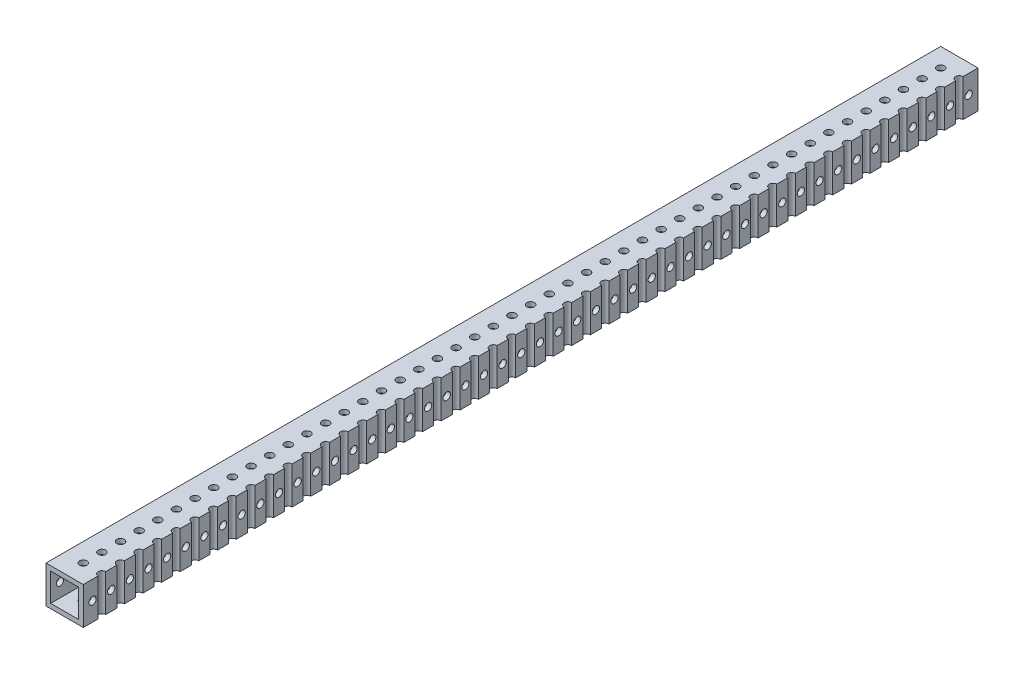
SolidWorks part; units mm, degrees
material "6061-T6 (SS)"
ref_plane "Front Plane" through (0, 0, 0) normal (0, 0, 1) x (1, 0, 0)
ref_plane "Top Plane" through (0, 0, 0) normal (0, 1, 0) x (1, 0, 0)
ref_plane "Right Plane" through (0, 0, 0) normal (1, 0, 0) x (0, 0, -1)
sketch "Sketch1" plane through (0, 0, 0) normal (0, 0, 1) x (1, 0, 0)
  line L0 (-9.525, 9.525) -> (9.525, 9.525)
  line L1 (-12.7, 12.7) -> (12.7, 12.7)
  line L2 (-12.7, 12.7) -> (-12.7, -12.7)
  line L3 (-12.7, -12.7) -> (12.7, -12.7)
  line L4 (12.7, 12.7) -> (12.7, -12.7)
  line L5 (9.525, 9.525) -> (9.525, -9.525)
  line L6 (-9.525, -9.525) -> (9.525, -9.525)
  line L7 (-9.525, 9.525) -> (-9.525, -9.525)
  line L8 (-12.7, 12.7) -> (12.7, -12.7) construction
  line L9 (12.7, 12.7) -> (-12.7, -12.7) construction
  point P5 (0, 0)
  dimension "D1" = 25.4
  dimension "D2" = 25.4
  dimension "D3" = 3.175
extrude "Boss-Extrude1" add sketch "Sketch1" along normal mid plane 609.6
sketch "Sketch2" plane through (0, 12.7, 0) normal (0, 1, 0) x (1, 0, 0)
  line L0 (12.7, -304.8) -> (-12.7, -304.8) construction
  line L1 (-12.7, -304.8) -> (-12.7, 304.8) construction
  line L2 (0, -292.1) -> (12.7, -292.1) construction
  line L3 (12.7, -292.1) -> (25.4, -292.1) construction
  line L4 (12.7, 304.8) -> (-12.7, 304.8) construction
  circle A0 centre (12.7, -292.1) radius 2.5527
  circle A1 centre (25.4, -292.1) radius 2.5527
  circle A2 centre (0, -292.1) radius 2.5527
  circle A3 centre (0, -279.4) radius 2.5527
  circle A4 centre (12.7, -279.4) radius 2.5527
  circle A5 centre (25.4, -279.4) radius 2.5527
  circle A6 centre (0, -266.7) radius 2.5527
  circle A7 centre (12.7, -266.7) radius 2.5527
  circle A8 centre (25.4, -266.7) radius 2.5527
  circle A9 centre (0, -254) radius 2.5527
  circle A10 centre (12.7, -254) radius 2.5527
  circle A11 centre (25.4, -254) radius 2.5527
  circle A12 centre (0, -241.3) radius 2.5527
  circle A13 centre (12.7, -241.3) radius 2.5527
  circle A14 centre (25.4, -241.3) radius 2.5527
  circle A15 centre (0, -228.6) radius 2.5527
  circle A16 centre (12.7, -228.6) radius 2.5527
  circle A17 centre (25.4, -228.6) radius 2.5527
  circle A18 centre (0, -215.9) radius 2.5527
  circle A19 centre (12.7, -215.9) radius 2.5527
  circle A20 centre (25.4, -215.9) radius 2.5527
  circle A21 centre (0, -203.2) radius 2.5527
  circle A22 centre (12.7, -203.2) radius 2.5527
  circle A23 centre (25.4, -203.2) radius 2.5527
  circle A24 centre (0, -190.5) radius 2.5527
  circle A25 centre (12.7, -190.5) radius 2.5527
  circle A26 centre (25.4, -190.5) radius 2.5527
  circle A27 centre (0, -177.8) radius 2.5527
  circle A28 centre (12.7, -177.8) radius 2.5527
  circle A29 centre (25.4, -177.8) radius 2.5527
  circle A30 centre (0, -165.1) radius 2.5527
  circle A31 centre (12.7, -165.1) radius 2.5527
  circle A32 centre (25.4, -165.1) radius 2.5527
  circle A33 centre (0, -152.4) radius 2.5527
  circle A34 centre (12.7, -152.4) radius 2.5527
  circle A35 centre (25.4, -152.4) radius 2.5527
  circle A36 centre (0, -139.7) radius 2.5527
  circle A37 centre (12.7, -139.7) radius 2.5527
  circle A38 centre (25.4, -139.7) radius 2.5527
  circle A39 centre (0, -127) radius 2.5527
  circle A40 centre (12.7, -127) radius 2.5527
  circle A41 centre (25.4, -127) radius 2.5527
  circle A42 centre (0, -114.3) radius 2.5527
  circle A43 centre (12.7, -114.3) radius 2.5527
  circle A44 centre (25.4, -114.3) radius 2.5527
  circle A45 centre (0, -101.6) radius 2.5527
  circle A46 centre (12.7, -101.6) radius 2.5527
  circle A47 centre (25.4, -101.6) radius 2.5527
  circle A48 centre (0, -88.9) radius 2.5527
  circle A49 centre (12.7, -88.9) radius 2.5527
  circle A50 centre (25.4, -88.9) radius 2.5527
  circle A51 centre (0, -76.2) radius 2.5527
  circle A52 centre (12.7, -76.2) radius 2.5527
  circle A53 centre (25.4, -76.2) radius 2.5527
  circle A54 centre (0, -63.5) radius 2.5527
  circle A55 centre (12.7, -63.5) radius 2.5527
  circle A56 centre (25.4, -63.5) radius 2.5527
  circle A57 centre (0, -50.8) radius 2.5527
  circle A58 centre (12.7, -50.8) radius 2.5527
  circle A59 centre (25.4, -50.8) radius 2.5527
  circle A60 centre (0, -38.1) radius 2.5527
  circle A61 centre (12.7, -38.1) radius 2.5527
  circle A62 centre (25.4, -38.1) radius 2.5527
  circle A63 centre (0, -25.4) radius 2.5527
  circle A64 centre (12.7, -25.4) radius 2.5527
  circle A65 centre (25.4, -25.4) radius 2.5527
  circle A66 centre (0, -12.7) radius 2.5527
  circle A67 centre (12.7, -12.7) radius 2.5527
  circle A68 centre (25.4, -12.7) radius 2.5527
  circle A69 centre (0, 0) radius 2.5527
  circle A70 centre (12.7, 0) radius 2.5527
  circle A71 centre (25.4, 0) radius 2.5527
  circle A72 centre (0, 12.7) radius 2.5527
  circle A73 centre (12.7, 12.7) radius 2.5527
  circle A74 centre (25.4, 12.7) radius 2.5527
  circle A75 centre (0, 25.4) radius 2.5527
  circle A76 centre (12.7, 25.4) radius 2.5527
  circle A77 centre (25.4, 25.4) radius 2.5527
  circle A78 centre (0, 38.1) radius 2.5527
  circle A79 centre (12.7, 38.1) radius 2.5527
  circle A80 centre (25.4, 38.1) radius 2.5527
  circle A81 centre (0, 50.8) radius 2.5527
  circle A82 centre (12.7, 50.8) radius 2.5527
  circle A83 centre (25.4, 50.8) radius 2.5527
  circle A84 centre (0, 63.5) radius 2.5527
  circle A85 centre (12.7, 63.5) radius 2.5527
  circle A86 centre (25.4, 63.5) radius 2.5527
  circle A87 centre (0, 76.2) radius 2.5527
  circle A88 centre (12.7, 76.2) radius 2.5527
  circle A89 centre (25.4, 76.2) radius 2.5527
  circle A90 centre (0, 88.9) radius 2.5527
  circle A91 centre (12.7, 88.9) radius 2.5527
  circle A92 centre (25.4, 88.9) radius 2.5527
  circle A93 centre (0, 101.6) radius 2.5527
  circle A94 centre (12.7, 101.6) radius 2.5527
  circle A95 centre (25.4, 101.6) radius 2.5527
  circle A96 centre (0, 114.3) radius 2.5527
  circle A97 centre (12.7, 114.3) radius 2.5527
  circle A98 centre (25.4, 114.3) radius 2.5527
  circle A99 centre (0, 127) radius 2.5527
  circle A100 centre (12.7, 127) radius 2.5527
  circle A101 centre (25.4, 127) radius 2.5527
  circle A108 centre (0, 152.4) radius 2.5527 [skipped]
  circle A109 centre (12.7, 152.4) radius 2.5527 [skipped]
  circle A110 centre (25.4, 152.4) radius 2.5527 [skipped]
  circle A111 centre (0, 139.7) radius 2.5527 [skipped]
  circle A112 centre (12.7, 139.7) radius 2.5527 [skipped]
  circle A113 centre (25.4, 139.7) radius 2.5527 [skipped]
  circle A114 centre (25.4, 139.7) radius 2.5527
  circle A115 centre (12.7, 139.7) radius 2.5527
  circle A116 centre (0, 139.7) radius 2.5527
  circle A117 centre (25.4, 152.4) radius 2.5527
  circle A118 centre (12.7, 152.4) radius 2.5527
  circle A119 centre (0, 152.4) radius 2.5527
  circle A120 centre (25.4, 165.1) radius 2.5527
  circle A121 centre (12.7, 165.1) radius 2.5527
  circle A122 centre (0, 165.1) radius 2.5527
  circle A123 centre (25.4, 177.8) radius 2.5527
  circle A124 centre (12.7, 177.8) radius 2.5527
  circle A125 centre (0, 177.8) radius 2.5527
  circle A126 centre (25.4, 190.5) radius 2.5527
  circle A127 centre (12.7, 190.5) radius 2.5527
  circle A128 centre (0, 190.5) radius 2.5527
  circle A129 centre (25.4, 203.2) radius 2.5527
  circle A130 centre (12.7, 203.2) radius 2.5527
  circle A131 centre (0, 203.2) radius 2.5527
  circle A132 centre (25.4, 215.9) radius 2.5527
  circle A133 centre (12.7, 215.9) radius 2.5527
  circle A134 centre (0, 215.9) radius 2.5527
  circle A135 centre (25.4, 228.6) radius 2.5527
  circle A136 centre (12.7, 228.6) radius 2.5527
  circle A137 centre (0, 228.6) radius 2.5527
  circle A138 centre (25.4, 241.3) radius 2.5527
  circle A139 centre (12.7, 241.3) radius 2.5527
  circle A140 centre (0, 241.3) radius 2.5527
  circle A141 centre (25.4, 254) radius 2.5527
  circle A142 centre (12.7, 254) radius 2.5527
  circle A143 centre (0, 254) radius 2.5527
  circle A144 centre (25.4, 266.7) radius 2.5527
  circle A145 centre (12.7, 266.7) radius 2.5527
  circle A146 centre (0, 266.7) radius 2.5527
  circle A147 centre (25.4, 279.4) radius 2.5527
  circle A148 centre (12.7, 279.4) radius 2.5527
  circle A149 centre (0, 279.4) radius 2.5527
  circle A150 centre (25.4, 292.1) radius 2.5527
  circle A151 centre (12.7, 292.1) radius 2.5527
  circle A152 centre (0, 292.1) radius 2.5527
  dimension "D2" = 5.1054
  dimension "D4" = 12.7
  dimension "D1" = 12.7
  dimension "D3" = 25.4
  dimension "D6" = 12.7
  dimension "D7" = 177.8
  dimension "D5" = 36
  dimension "D8" = 14
extrude "Cut-Extrude1" cut sketch "Sketch2" against normal through all
sketch "Sketch4" plane through (12.7, 0, 0) normal (1, 0, 0) x (0, 0, -1)
  line L1 (-304.8, -12.7) -> (-304.8, 12.7) construction
  line L2 (-304.8, -12.7) -> (-294.6527, -12.7) construction
  circle A2 centre (-298.45, 0) radius 2.4892
  circle A3 centre (-285.75, 0) radius 2.4892
  circle A16 centre (-273.05, 0) radius 2.4892
  circle A17 centre (-260.35, 0) radius 2.4892
  circle A18 centre (-247.65, 0) radius 2.4892
  circle A19 centre (133.35, 0) radius 2.4892
  circle A20 centre (146.05, 0) radius 2.4892
  circle A21 centre (158.75, 0) radius 2.4892
  circle A22 centre (171.45, 0) radius 2.4892
  circle A23 centre (184.15, 0) radius 2.4892
  circle A24 centre (196.85, 0) radius 2.4892
  circle A25 centre (209.55, 0) radius 2.4892
  circle A26 centre (222.25, 0) radius 2.4892
  circle A27 centre (234.95, 0) radius 2.4892
  circle A28 centre (247.65, 0) radius 2.4892
  circle A29 centre (260.35, 0) radius 2.4892
  circle A30 centre (273.05, 0) radius 2.4892
  circle A31 centre (285.75, 0) radius 2.4892
  circle A32 centre (298.45, 0) radius 2.4892
  circle A35 centre (-234.95, 0) radius 2.4892
  circle A36 centre (-222.25, 0) radius 2.4892
  circle A37 centre (-209.55, 0) radius 2.4892
  circle A38 centre (-196.85, 0) radius 2.4892
  circle A39 centre (-184.15, 0) radius 2.4892
  circle A40 centre (-171.45, 0) radius 2.4892
  circle A41 centre (-158.75, 0) radius 2.4892
  circle A42 centre (-146.05, 0) radius 2.4892
  circle A43 centre (-133.35, 0) radius 2.4892
  circle A44 centre (-120.65, 0) radius 2.4892
  circle A45 centre (-107.95, 0) radius 2.4892
  circle A46 centre (-95.25, 0) radius 2.4892
  circle A47 centre (-82.55, 0) radius 2.4892
  circle A48 centre (-69.85, 0) radius 2.4892
  circle A49 centre (-57.15, 0) radius 2.4892
  circle A50 centre (-44.45, 0) radius 2.4892
  circle A51 centre (-31.75, 0) radius 2.4892
  circle A52 centre (-19.05, 0) radius 2.4892
  circle A53 centre (-6.35, 0) radius 2.4892
  circle A54 centre (6.35, 0) radius 2.4892
  circle A55 centre (19.05, 0) radius 2.4892
  circle A56 centre (31.75, 0) radius 2.4892
  circle A57 centre (44.45, 0) radius 2.4892
  circle A58 centre (57.15, 0) radius 2.4892
  circle A59 centre (69.85, 0) radius 2.4892
  circle A60 centre (82.55, 0) radius 2.4892
  circle A61 centre (95.25, 0) radius 2.4892
  circle A62 centre (107.95, 0) radius 2.4892
  circle A63 centre (120.65, 0) radius 2.4892
  dimension "D2" = 4.9784
  dimension "D1" = 6.35
  dimension "D3" = 12.7
  dimension "D4" = 12.7
  dimension "D5" = 34
  dimension "D6" = 10
  dimension "D7" = 6
extrude "Cut-Extrude3" cut sketch "Sketch4" against normal through all
